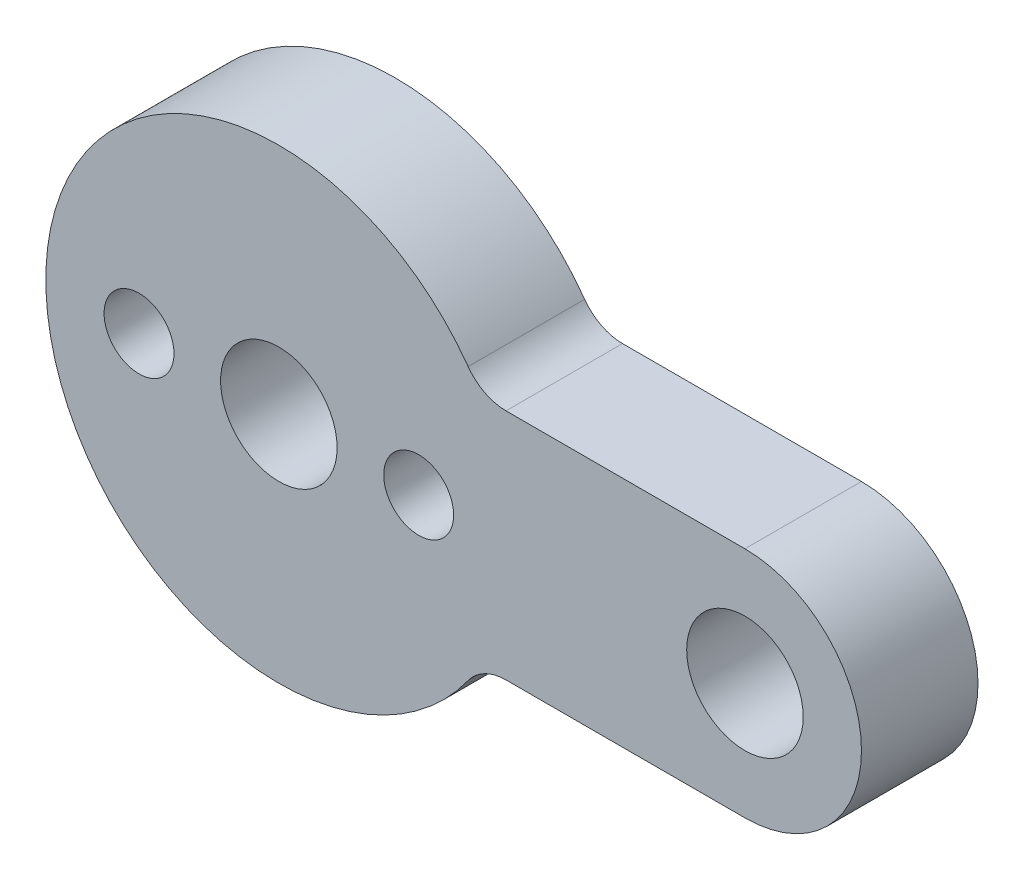
SolidWorks part; units mm, degrees
ref_plane "前视基准面" through (0, 0, 0) normal (0, 0, 1) x (1, 0, 0)
ref_plane "上视基准面" through (0, 0, 0) normal (0, 1, 0) x (1, 0, 0)
ref_plane "右视基准面" through (0, 0, 0) normal (1, 0, 0) x (0, 0, -1)
sketch "草图1" plane through (0, 0, 0) normal (0, 0, 1) x (1, 0, 0)
  line L0 (0, 0) -> (-40, 0) construction
  line L1 (0, -5) -> (-40, -5)
  line L2 (0, 5) -> (-40, 5)
  arc A0 (0, -5) -> (0, 5) centre (0, 0) ccw
  arc A1 (-40, 5) -> (-40, -5) centre (-40, 0) ccw
  circle A2 centre (-20, 0) radius 2.5
  circle A3 centre (-40, 0) radius 2.5
  circle A4 centre (0, 0) radius 2.5
  point P3 (-20, 0)
  dimension "D1" = 5
  dimension "D2" = 5
  dimension "D3" = 5
  dimension "D4" = 5
  dimension "D5" = 40
extrude "凸台-拉伸1" add sketch "草图1" along normal blind 5
sketch "草图2" plane through (0, 0, 0) normal (0, 0, -1) x (-1, 0, 0)
  circle A0 centre (40, 0) radius 2.5
  circle A1 centre (40, 0) radius 5
  circle A2 centre (0, 0) radius 2.5
  circle A3 centre (0, 0) radius 5
extrude "凸台-拉伸2" add sketch "草图2" along normal blind 12.8
sketch "草图3" plane through (0, 0, 5) normal (0, 0, 1) x (1, 0, 0)
  line L0 (-26, 0) -> (-14, 0) construction
  circle A0 centre (-26, 0) radius 1.5
  circle A1 centre (-14, 0) radius 1.5
  circle A2 centre (-20, 0) radius 2.5 construction
  point P4 (-20, 0)
  dimension "D1" = 3
  dimension "D2" = 3
  dimension "D3" = 12
  dimension "D4" = 0
extrude "切除-拉伸1" cut sketch "草图3" against normal blind 13
sketch "草图4" plane through (0, 0, 5) normal (0, 0, 1) x (1, 0, 0)
  line L1 (-29.4849, 3.1681) -> (-10.5151, 3.1681)
  line L3 (-29.5488, -2.9698) -> (-10.4512, -2.9698)
  arc A0 (-29.5488, -2.9698) -> (-10.4512, -2.9698) centre (-20, 0) ccw
  arc A1 (-10.5151, 3.1681) -> (-29.4849, 3.1681) centre (-20, 0) ccw
  dimension "D1" = 20
extrude "凸台-拉伸3" add sketch "草图4" against normal up to vertex up to point (0, 5, 0)
fillet "圆角1" radius 2 4 edges at (-28.6603, -5, 2.5) (-11.3397, -5, 2.5) (-11.3397, 5, 2.5) (-28.6603, 5, 2.5)
sketch "草图6" plane through (0, 0, 0) normal (0, 0, -1) x (-1, 0, 0)
  line L1 (28.1223, 5.8333) -> (47.0186, 5.8333)
  line L3 (28.1223, -5.8333) -> (47.0186, -5.8333)
  line L4 (47.0186, 5.8333) -> (47.0186, -5.8333)
  arc A0 (28.1223, 5.8333) -> (28.1223, -5.8333) centre (20, 0) cw
  arc A1 (28.1223, 5.8333) -> (11.8777, 5.8333) centre (20, 0) ccw construction
extrude "切除-拉伸2" cut sketch "草图6" against normal blind 10 and the other way blind 16
sketch "草图7" plane through (0, 0, 0) normal (0, 0, -1) x (-1, 0, 0)
  circle A0 centre (0, 0) radius 5
extrude "切除-拉伸3" cut sketch "草图7" along normal blind 14
